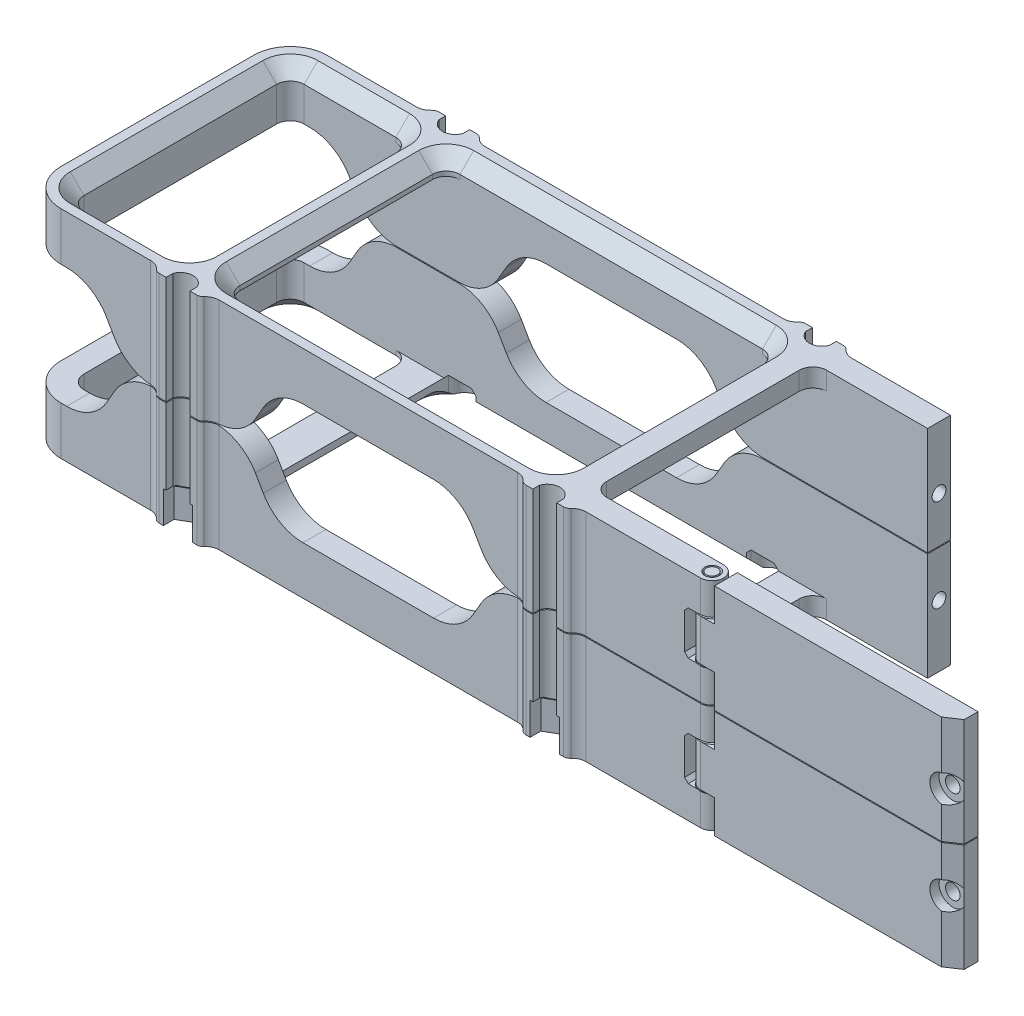
SolidWorks part; units mm, degrees
ref_plane "Płaszczyzna przednia" through (0, 0, 0) normal (0, 0, 1) x (1, 0, 0)
ref_plane "Płaszczyzna górna" through (0, 0, 0) normal (0, 1, 0) x (1, 0, 0)
ref_plane "Płaszczyzna prawa" through (0, 0, 0) normal (1, 0, 0) x (0, 0, -1)
sketch "Szkic1" plane through (0, 0, 0) normal (0, 1, 0) x (1, 0, 0)
  line L0 (-70, -24) -> (75, -24)
  line L1 (75, -24) -> (75, -29)
  line L3 (-75, -29) -> (-75, -24)
  line L4 (75, -29) -> (45.6, -29)
  line L5 (0, 29) -> (0, -29) construction
  line L6 (-34.4, -29) -> (34.4, -29)
  line L7 (-75, -29) -> (-45.6, -29)
  line L8 (-45.6, -29) -> (-40, -29) construction
  line L9 (-40, -29) -> (-34.4, -29) construction
  line L10 (34.4, -29) -> (40, -29) construction
  line L11 (45.6, -29) -> (40, -29) construction
  line L12 (-55, 0) -> (55, 0) construction
  line L13 (45.6, 29) -> (40, 29) construction
  line L14 (34.4, 29) -> (40, 29) construction
  line L15 (-40, 29) -> (-34.4, 29) construction
  line L16 (-45.6, 29) -> (-40, 29) construction
  line L17 (-75, 29) -> (-45.6, 29)
  line L18 (-34.4, 29) -> (34.4, 29)
  line L19 (69, 29) -> (45.6, 29)
  line L20 (-75, 29) -> (-75, 24)
  line L21 (75, 24) -> (75, 29) construction
  line L22 (-70, 24) -> (69, 24)
  line L23 (-75, 24) -> (-75, -24)
  line L24 (-70, 24) -> (-70, -24)
  line L25 (-75, 24) -> (-70, 24) construction
  line L26 (-75, -24) -> (-70, -24) construction
  line L27 (69, 29) -> (69, 24)
  line L28 (69, 24) -> (75, 24) construction
  line L29 (75, 29) -> (69, 29) construction
  arc A0 (-45.6, -29) -> (-34.4, -29) centre (-40, -29) ccw
  arc A1 (34.4, -29) -> (45.6, -29) centre (40, -29) ccw
  arc A2 (-34.4, -29) -> (-45.6, -29) centre (-40, -29) ccw construction
  arc A3 (45.6, -29) -> (34.4, -29) centre (40, -29) ccw construction
  arc A4 (45.6, 29) -> (34.4, 29) centre (40, 29) cw construction
  arc A5 (-34.4, 29) -> (-45.6, 29) centre (-40, 29) cw construction
  arc A6 (34.4, 29) -> (45.6, 29) centre (40, 29) cw
  arc A7 (-45.6, 29) -> (-34.4, 29) centre (-40, 29) cw
  point P4 (0, 0)
  point P12 (0, 0)
  point P16 (0, -29)
  point P31 (0, 29)
  dimension "D1" = 11.2
  dimension "D2" = 11.2
  dimension "D3" = 80
  dimension "D4" = 150
  dimension "D6" = 58
  dimension "D7" = 5
  dimension "D5" = 48
  dimension "D8" = 6
extrude "Dodanie-wyciągnięcie1" add sketch "Szkic1" along normal blind 23.5 separate body
sketch "Szkic2" plane through (0, 23.5, 0) normal (0, 1, 0) x (1, 0, 0)
  line L0 (-45.6, -29) -> (-42.6, -29) construction
  line L3 (-37.4, -29) -> (-34.4, -29) construction
  line L4 (-44.1, -30.5) -> (-42.6, -30.5)
  line L5 (-42.6, -29) -> (-42.6, -30.5)
  line L6 (-37.4, -29) -> (-37.4, -30.5)
  line L7 (-42.6, -30.5) -> (-42.1237, -30.5) construction
  line L8 (-42.1237, -30.5) -> (-37.8763, -30.5) construction
  line L9 (-37.8763, -30.5) -> (-37.4, -30.5) construction
  line L10 (-37.4, -30.5) -> (-35.9, -30.5)
  line L12 (-12.925, 0) -> (12.925, 0) construction
  line L13 (-37.8763, 30.5) -> (-37.4, 30.5) construction
  line L14 (-42.1237, 30.5) -> (-37.8763, 30.5) construction
  line L15 (-42.6, 30.5) -> (-42.1237, 30.5) construction
  line L16 (-37.4, 29) -> (-34.4, 29) construction
  line L22 (-45.6, 29) -> (-42.6, 29) construction
  line L23 (-37.4, 30.5) -> (-35.9, 30.5)
  line L24 (-37.4, 29) -> (-37.4, 30.5)
  line L25 (-42.6, 29) -> (-42.6, 30.5)
  line L26 (-44.1, 30.5) -> (-42.6, 30.5)
  line L27 (0, -12.925) -> (0, 12.925) construction
  line L28 (45.6, 29) -> (42.6, 29) construction
  line L29 (37.4, 29) -> (34.4, 29) construction
  line L30 (42.6, 30.5) -> (42.1237, 30.5) construction
  line L31 (42.1237, 30.5) -> (37.8763, 30.5) construction
  line L40 (37.8763, 30.5) -> (37.4, 30.5) construction
  line L41 (37.8763, -30.5) -> (37.4, -30.5) construction
  line L42 (42.1237, -30.5) -> (37.8763, -30.5) construction
  line L43 (42.6, -30.5) -> (42.1237, -30.5) construction
  line L44 (37.4, -29) -> (34.4, -29) construction
  line L45 (45.6, -29) -> (42.6, -29) construction
  line L46 (44.1, 30.5) -> (42.6, 30.5)
  line L47 (42.6, 29) -> (42.6, 30.5)
  line L48 (37.4, 29) -> (37.4, 30.5)
  line L49 (37.4, 30.5) -> (35.9, 30.5)
  line L50 (37.4, -30.5) -> (35.9, -30.5)
  line L51 (37.4, -29) -> (37.4, -30.5)
  line L52 (42.6, -29) -> (42.6, -30.5)
  line L53 (44.1, -30.5) -> (42.6, -30.5)
  arc A3 (-42.1237, -30.5) -> (-37.8763, -30.5) centre (-40, -29) ccw construction
  arc A4 (-45.6, -29) -> (-44.1, -30.5) centre (-44.1, -29) ccw
  arc A5 (-34.4, -29) -> (-35.9, -30.5) centre (-35.9, -29) cw
  arc A6 (-45.6, -29) -> (-34.4, -29) centre (-40, -29) ccw
  arc A7 (-42.6, -29) -> (-42.1237, -30.5) centre (-40, -29) ccw construction
  arc A8 (-37.8763, -30.5) -> (-37.4, -29) centre (-40, -29) ccw construction
  arc A10 (-37.8763, 30.5) -> (-37.4, 29) centre (-40, 29) cw construction
  arc A11 (-42.6, 29) -> (-42.1237, 30.5) centre (-40, 29) cw construction
  arc A12 (-42.1237, 30.5) -> (-37.8763, 30.5) centre (-40, 29) cw construction
  arc A17 (-42.6, 29) -> (-37.4, 29) centre (-40, 30) ccw
  arc A18 (-45.6, 29) -> (-34.4, 29) centre (-40, 29) cw
  arc A19 (-34.4, 29) -> (-35.9, 30.5) centre (-35.9, 29) ccw
  arc A20 (-45.6, 29) -> (-44.1, 30.5) centre (-44.1, 29) cw
  arc A21 (42.1237, 30.5) -> (37.8763, 30.5) centre (40, 29) ccw construction
  arc A22 (42.6, 29) -> (42.1237, 30.5) centre (40, 29) ccw construction
  arc A31 (-42.6, -29) -> (-37.4, -29) centre (-40, -30) cw
  arc A32 (37.8763, 30.5) -> (37.4, 29) centre (40, 29) ccw construction
  arc A33 (37.8763, -30.5) -> (37.4, -29) centre (40, -29) cw construction
  arc A34 (42.6, -29) -> (42.1237, -30.5) centre (40, -29) cw construction
  arc A35 (42.1237, -30.5) -> (37.8763, -30.5) centre (40, -29) cw construction
  arc A36 (42.6, -29) -> (37.4, -29) centre (40, -30) ccw
  arc A37 (45.6, 29) -> (44.1, 30.5) centre (44.1, 29) ccw
  arc A38 (34.4, 29) -> (35.9, 30.5) centre (35.9, 29) cw
  arc A39 (45.6, 29) -> (34.4, 29) centre (40, 29) ccw
  arc A40 (42.6, 29) -> (37.4, 29) centre (40, 30) cw
  arc A41 (45.6, -29) -> (34.4, -29) centre (40, -29) cw
  arc A42 (34.4, -29) -> (35.9, -30.5) centre (35.9, -29) ccw
  arc A43 (45.6, -29) -> (44.1, -30.5) centre (44.1, -29) cw
  dimension "D1" = 5.2
  dimension "D2" = 1
extrude "Wytnij-wyciągnięcie1" cut sketch "Szkic2" against normal through all
fillet "Zaokrąglenie1" radius 8 2 edges at (-75, 11.75, -29) (-75, 11.75, 29)
fillet "Zaokrąglenie2" radius 3 2 edges at (-70, 11.75, -24) (-70, 11.75, 24)
fillet "Zaokrąglenie3" radius 3 8 edges at (-34.4, 11.75, 29) (-45.6, 11.75, 29) (-45.6, 11.75, -29) (-34.4, 11.75, -29) (34.4, 11.75, -29) (45.6, 11.75, -29) (45.6, 11.75, 29) (34.4, 11.75, 29)
sketch "Szkic6" plane through (0, 23.5, 0) normal (0, 1, 0) x (1, 0, 0)
  line L0 (72.5, -26.5) -> (72.5, -24) construction
  line L1 (75, -24) -> (-67, -24) construction
  line L2 (72.5, -24) -> (75, -24) construction
  circle A0 centre (72.5, -26.5) radius 1.6
  dimension "D3" = 3.2
  dimension "D1" = 2.5
  dimension "D2" = 2.5
extrude "Wytnij-wyciągnięcie4" cut sketch "Szkic6" against normal through all
sketch "Szkic7" plane through (0, 0, 29) normal (0, 0, 1) x (1, 0, 0)
  line L0 (75, 0) -> (75, 7) construction
  line L1 (75, 23.5) -> (75, 0) construction
  line L2 (75, 7) -> (69, 7)
  line L3 (69, 7) -> (69, 16.5)
  line L4 (69, 16.5) -> (75, 16.5)
  line L5 (75, 16.5) -> (75, 7)
  dimension "D1" = 7
  dimension "D2" = 9.5
  dimension "D3" = 6
extrude "Wytnij-wyciągnięcie5" cut sketch "Szkic7" against normal through all
chamfer "Sfazowanie1" distance 1 angle 45 2 edges at (72.5, 16.5, 28.1) (72.5, 7, 24.9)
sketch "Szkic8" plane through (0, 0, 0) normal (0, -1, 0) x (1, 0, 0)
  circle A0 centre (72.5, 26.5) radius 1.25
  dimension "D1" = 2.5
extrude "Dodanie-wyciągnięcie2" add sketch "Szkic8" against normal blind 23.5 separate body
ref_plane "Płaszczyzna1" through (0, 7.2, 0) normal (0, 1, 0) x (1, 0, 0)
sketch "Szkic9" plane through (0, 7.2, 0) normal (0, 1, 0) x (1, 0, 0)
  circle A0 centre (72.5, -26.5) radius 2.5
  dimension "D1" = 5
extrude "Dodanie-wyciągnięcie3" add sketch "Szkic9" along normal blind 9.1
chamfer "Sfazowanie2" distance 1.25 angle 45 2 edges at (71.25, 7.2, 26.5) (71.25, 16.3, 26.5)
sketch "Szkic10" plane through (0, 0, 0) normal (0, 1, 0) x (1, 0, 0)
  line L0 (0, 0) -> (70, 0) construction
  line L1 (70, 0) -> (70, 29)
  line L2 (70, 29) -> (75, 29)
  line L3 (75, 29) -> (75, -23.5)
  line L4 (75, -23.5) -> (70, -23.5)
  line L5 (70, -23.5) -> (70, 0)
  dimension "D1" = 70
  dimension "D2" = 5
  dimension "D3" = 29
  dimension "D4" = 23.5
extrude "Dodanie-wyciągnięcie4" add sketch "Szkic10" along normal blind 23.5 separate body
sketch "Szkic12" plane through (0, 7.2, 0) normal (0, 1, 0) x (1, 0, 0)
  line L0 (75, -26.5) -> (75, -23.5)
  line L1 (70, -23.5) -> (75, -23.5) construction
  line L2 (70, -26.5) -> (70, -23.5)
  line L3 (70, -23.5) -> (75, -23.5)
  arc A0 (70, -26.5) -> (75, -26.5) centre (72.5, -26.5) ccw
  arc A1 (75, -26.5) -> (70, -26.5) centre (72.5, -26.5) ccw construction
  dimension "D1" = 5
extrude "Dodanie-wyciągnięcie5" add sketch "Szkic12" along normal blind 9.1
fillet "Zaokrąglenie4" radius 2.5 4 edges at (75, 3.5, 24) (75, 3.5, 29) (75, 20, 29) (75, 20, 24)
ref_axis "Oś1" through (72.5, 25.0302, 26.5) along (0, -1, 0)
sketch "Szkic13" plane through (75, 0, 0) normal (1, 0, 0) x (0, 0, -1)
  line L0 (29, 23.5) -> (29, 0) construction
  line L2 (-23.5, 23.5) -> (29, 23.5) construction
  circle A0 centre (26.5, 13.5) radius 1.6
  dimension "D2" = 10
  dimension "D3" = 3.2
  dimension "D1" = 2.5
extrude "Wytnij-wyciągnięcie6" cut sketch "Szkic13" against normal up to next (5 mm away)
sketch "Szkic14" plane through (69, 0, 0) normal (1, 0, 0) x (0, 0, -1)
  circle A0 centre (26.5, 13.5) radius 1.5
  dimension "D1" = 3
extrude "Wytnij-wyciągnięcie7" cut sketch "Szkic14" against normal blind 10
sketch "Szkic15" plane through (75, 0, 0) normal (1, 0, 0) x (0, 0, -1)
  circle A0 centre (26.5, 13.5) radius 3
  dimension "D1" = 6
chamfer "Sfazowanie3" distance 3 distance2 2 1 edges at (75, 11.75, -29) first distance on face at (75, 13.5, -28.1)
extrude "Wytnij-wyciągnięcie8" cut sketch "Szkic15" against normal blind 2
chamfer "Sfazowanie4" distance 0.8 angle 45 2 edges at (69, 16.5, 26.5) (69, 7, 26.5)
move or copy body "Obiekt-Przenieś/Kopiuj1" bodies to move or copy 114 copy no rotation origin (72.5, 0, 26.5) rotation axis (0, -1, 0) rotation angle 90
sketch "Szkic16" plane through (0, 0, 0) normal (0, -1, 0) x (1, 0, 0)
  line L0 (-40, 0) -> (40, 0) construction
  line L1 (40, 24) -> (40, -24) construction
  line L2 (-67, -24) -> (69, -24) construction
  line L4 (72.5, 24) -> (-67, 24) construction
  line L5 (44, 24) -> (44, -24)
  line L6 (44, -24) -> (40, -24)
  line L7 (36, 24) -> (44, 24)
  line L8 (36, 24) -> (36, -24)
  line L9 (36, -24) -> (40, -24)
  line L10 (0, -12.925) -> (0, 12.925) construction
  line L11 (-44, -24) -> (-40, -24)
  line L12 (-36, -24) -> (-40, -24)
  line L13 (-44, 24) -> (-44, -24)
  line L14 (-36, 24) -> (-44, 24)
  line L15 (-36, 24) -> (-36, -24)
  point P4 (0, 0)
  point P10 (40, 0)
  point P17 (40, 24)
  dimension "D1" = 80
  dimension "D2" = 8
extrude "Dodanie-wyciągnięcie6" add sketch "Szkic16" against normal blind 4
sketch "Szkic17" plane through (0, 0, 29) normal (0, 0, 1) x (1, 0, 0)
  line L0 (-75, 10.5) -> (-60, 10.5)
  line L1 (-75, 0) -> (-75, 23.5) construction
  line L2 (-60, 10.5) -> (-52.4944, 23.5)
  line L3 (-67, 23.5) -> (-47.4541, 23.5) construction
  line L4 (-52.4944, 23.5) -> (-75, 23.5)
  line L5 (-75, 23.5) -> (-75, 10.5)
  dimension "D1" = 15
  dimension "D2" = 60
  dimension "D3" = 13
extrude "Wytnij-wyciągnięcie9" cut sketch "Szkic17" against normal through all
sketch "Szkic18" plane through (0, 0, 29) normal (0, 0, 1) x (1, 0, 0)
  line L0 (-27.5056, 23.5) -> (-20, 10.5)
  line L1 (-32.5459, 23.5) -> (32.5459, 23.5) construction
  line L2 (0, 0) -> (0, 10.5) construction
  line L3 (-32.5459, 0) -> (32.5459, 0) construction
  line L4 (20, 10.5) -> (-20, 10.5)
  line L5 (20, 10.5) -> (27.5056, 23.5)
  line L6 (27.5056, 23.5) -> (-27.5056, 23.5)
  point P11 (0, 10.5)
  dimension "D1" = 60
  dimension "D2" = 60
  dimension "D3" = 40
  dimension "D4" = 13
extrude "Wytnij-wyciągnięcie10" cut sketch "Szkic18" against normal through all
fillet "Zaokrąglenie5" radius 10 12 edges at (-52.4944, 23.5, -26.5) (-52.4944, 23.5, 26.5) (-27.5056, 23.5, 26.5) (-20, 10.5, 26.5) (20, 10.5, 26.5) (27.5056, 23.5, 26.5) (-27.5056, 23.5, -26.5) (-20, 10.5, -26.5) (20, 10.5, -26.5) (27.5056, 23.5, -26.5) (-60, 10.5, -26.5) (-60, 10.5, 26.5)
fillet "Zaokrąglenie6" radius 3 8 edges at (-44, 2, -24) (-44, 2, 24) (-36, 2, 24) (-36, 2, -24) (36, 2, -24) (44, 2, -24) (36, 2, 24) (44, 2, 24)
chamfer "Sfazowanie5" distance 3 angle 45 16 edges at (-44, 0, 0) (-44.8787, 0, 23.1213) (-44.8787, 0, -23.1213) (-57, 0, 24) (-57, 0, -24) (-69.1213, 0, 23.1213) (-69.1213, 0, -23.1213) (-70, 0, 0) (36, 0, 0) (35.1213, 0, -23.1213) (35.1213, 0, 23.1213) (0, 0, -24) (0, 0, 24) (-35.1213, 0, -23.1213) (-35.1213, 0, 23.1213) (-36, 0, 0)
ref_plane "Płaszczyzna2" through (0, 23.6, 0) normal (0, 1, 0) x (1, 0, 0)
mirror "Lustro1" about plane through (0, 23.6, 0) normal (0, 1, 0) of bodies 118 111
sketch "Szkic19" plane through (0, 0, 0) normal (0, -1, 0) x (1, 0, 0)
  line L1 (40, -26.305) -> (36.8, -28.1525)
  line L2 (36.8, -28.1525) -> (36.8, -31.8475)
  line L3 (36.8, -31.8475) -> (40, -33.695)
  line L4 (40, -33.695) -> (43.2, -31.8475)
  line L5 (43.2, -31.8475) -> (43.2, -28.1525)
  line L6 (43.2, -28.1525) -> (40, -26.305)
  line L7 (-40, -26.305) -> (-43.2, -28.1525)
  line L8 (-43.2, -28.1525) -> (-43.2, -31.8475)
  line L9 (-43.2, -31.8475) -> (-40, -33.695)
  line L10 (-40, -33.695) -> (-36.8, -31.8475)
  line L11 (-36.8, -31.8475) -> (-36.8, -28.1525)
  line L12 (-36.8, -28.1525) -> (-40, -26.305)
  line L13 (-40, 26.305) -> (-36.8, 28.1525)
  line L14 (-36.8, 28.1525) -> (-36.8, 31.8475)
  line L15 (-36.8, 31.8475) -> (-40, 33.695)
  line L16 (-40, 33.695) -> (-43.2, 31.8475)
  line L17 (-43.2, 31.8475) -> (-43.2, 28.1525)
  line L18 (-43.2, 28.1525) -> (-40, 26.305)
  line L19 (40, 26.305) -> (43.2, 28.1525)
  line L20 (43.2, 28.1525) -> (43.2, 31.8475)
  line L21 (43.2, 31.8475) -> (40, 33.695)
  line L22 (40, 33.695) -> (36.8, 31.8475)
  line L23 (36.8, 31.8475) -> (36.8, 28.1525)
  line L24 (36.8, 28.1525) -> (40, 26.305)
  circle A0 centre (40, -30) radius 3.2 construction
  circle A1 centre (-40, -30) radius 3.2 construction
  circle A2 centre (-40, 30) radius 3.2 construction
  circle A3 centre (40, 30) radius 3.2 construction
  dimension "D1" = 6.4
  dimension "D2" = 6.4
  dimension "D3" = 6.4
  dimension "D4" = 6.4
extrude "Wytnij-wyciągnięcie11" cut sketch "Szkic19" against normal blind 7
chamfer "Sfazowanie6" distance 0.7 angle 45 8 edges at (-38.4, 7, 27.2287) (-41.6, 7, 27.2287) (-41.6, 7, -27.2287) (-38.4, 7, -27.2287) (38.4, 7, -27.2287) (41.6, 7, -27.2287) (41.6, 7, 27.2287) (38.4, 7, 27.2287)
sketch "Szkic20" plane through (0, 0, 0) normal (0, -1, 0) x (1, 0, 0)
  line L0 (0, 0) -> (33, 0) construction
  line L1 (33, 25) -> (33, -25) construction
  line L2 (36.5, 25) -> (36.5, -25)
  line L3 (29.5, 25) -> (29.5, -25)
  line L5 (0, -12.925) -> (0, 12.925) construction
  line L6 (-33, 25) -> (-33, -25) construction
  line L7 (-36.5, 25) -> (-36.5, -25)
  line L8 (-29.5, 25) -> (-29.5, -25)
  arc A0 (36.5, 25) -> (29.5, 25) centre (33, 25) ccw
  arc A1 (29.5, -25) -> (36.5, -25) centre (33, -25) ccw
  arc A2 (-36.5, 25) -> (-29.5, 25) centre (-33, 25) cw
  arc A3 (-29.5, -25) -> (-36.5, -25) centre (-33, -25) cw
  point P5 (33, 0)
  point P16 (-33, 0)
  dimension "D1" = 7
  dimension "D2" = 33
  dimension "D3" = 50
extrude "Wytnij-wyciągnięcie12" cut sketch "Szkic20" against normal blind 5
chamfer "Sfazowanie7" distance 1 angle 45 12 edges at (36.5, 5, 24.5) (29.5, 5, 24.5) (33, 5, 28.5) (29.5, 5, -24.5) (36.5, 5, -24.5) (33, 5, -28.5) (-29.5, 5, 24.5) (-36.5, 5, 24.5) (-33, 5, 28.5) (-36.5, 5, -24.5) (-29.5, 5, -24.5) (-33, 5, -28.5)
equation "\"Rod_diameter\"= 5.2"
equation "\"D2@Szkic1\"=\"Rod_diameter\"+6"
equation "\"D1@Szkic2\"=\"Rod_diameter\""
equation "\"height\"=23.5"
equation "\"D1@Dodanie-wyciągnięcie1\"=\"height\""
equation "\"D2@Szkic7\"=\"height\"-7*2"
equation "\"D1@Dodanie-wyciągnięcie3\"=\"height\"-2*7-0.4"
equation "\"D1@Dodanie-wyciągnięcie5\"=\"height\"-2*7-0.4"
equation "\"D1@Dodanie-wyciągnięcie2\"=\"height\""
